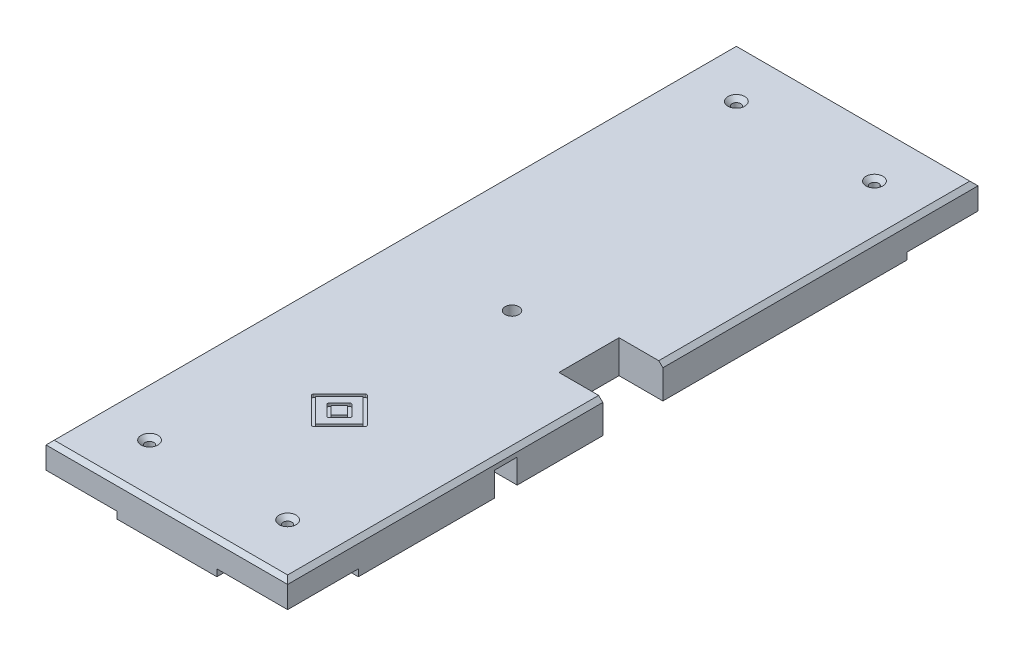
SolidWorks part; units mm, degrees
ref_plane "Front Plane" through (0, 0, 0) normal (0, 0, 1) x (1, 0, 0)
ref_plane "Top Plane" through (0, 0, 0) normal (0, 1, 0) x (1, 0, 0)
ref_plane "Right Plane" through (0, 0, 0) normal (1, 0, 0) x (0, 0, -1)
sketch "Sketch1" plane through (0, -20.7207, 0) normal (0, 1, 0) x (1, 0, 0)
  line L3 (6.005, -235.0339) -> (6.005, -194.0339)
  line L4 (6.005, -194.0339) -> (47.005, -194.0339)
  line L12 (47.005, 123.9661) -> (6.005, 123.9661)
  line L13 (47.005, -194.0339) -> (47.005, 123.9661)
  line L14 (6.005, -194.0339) -> (47.005, -194.0339)
  line L15 (6.005, -235.0339) -> (6.005, -194.0339)
  line L16 (-51.995, -235.0339) -> (6.005, -235.0339)
  line L17 (-51.995, -194.0339) -> (-51.995, -235.0339)
  line L18 (-92.995, -194.0339) -> (-51.995, -194.0339)
  line L19 (-92.995, 123.9661) -> (-92.995, -194.0339)
  line L20 (-51.995, 123.9661) -> (-92.995, 123.9661)
  line L21 (-51.995, 164.9661) -> (-51.995, 123.9661)
  line L22 (6.005, 164.9661) -> (-51.995, 164.9661)
  line L23 (6.005, 123.9661) -> (6.005, 164.9661)
  line L24 (47.005, 123.9661) -> (6.005, 123.9661)
  line L25 (47.005, -194.0339) -> (47.005, 123.9661)
  line L28 (-51.995, -235.0339) -> (6.005, -235.0339)
  line L29 (-51.995, -194.0339) -> (-51.995, -235.0339)
  line L30 (-92.995, -194.0339) -> (-51.995, -194.0339)
  line L31 (-92.995, 123.9661) -> (-92.995, -194.0339)
  line L32 (-51.995, 123.9661) -> (-92.995, 123.9661)
  line L33 (-51.995, 164.9661) -> (-51.995, 123.9661)
  line L34 (6.005, 164.9661) -> (-51.995, 164.9661)
  line L35 (6.005, 123.9661) -> (6.005, 164.9661)
  circle A1 centre (17.005, -225.0339) radius 2.5
  circle A2 centre (17.005, -225.0339) radius 2.5
  circle A3 centre (37.005, -205.0339) radius 2.5
  circle A4 centre (37.005, -205.0339) radius 2.5
  circle A5 centre (17.005, -205.0339) radius 2.5
  circle A6 centre (17.005, -205.0339) radius 2.5
  circle A7 centre (-62.995, -205.0339) radius 2.5
  circle A8 centre (-62.995, -205.0339) radius 2.5
  circle A9 centre (-62.995, -225.0339) radius 2.5
  circle A10 centre (-62.995, -225.0339) radius 2.5
  circle A11 centre (-82.995, -225.0339) radius 2.5
  circle A12 centre (-82.995, -225.0339) radius 2.5
  circle A13 centre (-82.995, -205.0339) radius 2.5
  circle A14 centre (-82.995, -205.0339) radius 2.5
  circle A15 centre (-62.995, 134.9661) radius 2.5
  circle A16 centre (-62.995, 134.9661) radius 2.5
  circle A17 centre (-62.995, 154.9661) radius 2.5
  circle A18 centre (-62.995, 154.9661) radius 2.5
  circle A19 centre (-82.995, 154.9661) radius 2.5
  circle A20 centre (-82.995, 154.9661) radius 2.5
  circle A21 centre (37.005, 134.9661) radius 2.5
  circle A22 centre (37.005, 134.9661) radius 2.5
  circle A23 centre (17.005, 134.9661) radius 2.5
  circle A24 centre (17.005, 134.9661) radius 2.5
  circle A25 centre (17.005, 154.9661) radius 2.5
  circle A26 centre (17.005, 154.9661) radius 2.5
  circle A27 centre (37.005, 154.9661) radius 2.5
  circle A28 centre (37.005, 154.9661) radius 2.5
  circle A29 centre (-82.995, 134.9661) radius 2.5
  circle A30 centre (-82.995, 134.9661) radius 2.5
  dimension "D1" = 0
  dimension "D2" = 0
  dimension "D3" = 0
  dimension "D4" = 0
  dimension "D5" = 0
  dimension "D6" = 0
  dimension "D7" = 0
  dimension "D8" = 0
  dimension "D9" = 0
  dimension "D10" = 0
  dimension "D11" = 0
  dimension "D12" = 0
  dimension "D13" = 0
  dimension "D14" = 0
  dimension "D15" = 0
  dimension "D16" = 0
extrude "Boss-Extrude1" add sketch "Sketch1" against normal up to surface (4 mm away) contours L31 L30 L29 L28 L3 L4 L25 L24 L35 L34 L33 L32
sketch "Sketch2" plane through (0, -20.7207, 0) normal (0, 1, 0) x (1, 0, 0)
  line L0 (-92.995, 164.9661) -> (47.005, 164.9661)
  line L1 (-92.995, 164.9661) -> (-92.995, -235.0339)
  line L2 (47.005, 164.9661) -> (47.005, -235.0339)
  line L3 (-92.995, -235.0339) -> (47.005, -235.0339)
  line L4 (-52.995, -235.0339) -> (-92.995, -235.0339) construction
extrude "Boss-Extrude2" add sketch "Sketch2" along normal blind 15.05
sketch "Sketch3" plane through (0, -20.7207, 0) normal (0, -1, 0) x (1, 0, 0)
  line L0 (-56.995, 225.0339) -> (-86.995, 225.0339) construction
  line L1 (-86.995, 229.0339) -> (-78.995, 229.0339)
  line L2 (-86.995, 229.0339) -> (-86.995, 199.0339)
  line L3 (-86.995, 199.0339) -> (-78.995, 199.0339)
  line L4 (-78.995, 229.0339) -> (-78.995, 199.0339)
  line L5 (-56.995, 221.0339) -> (-86.995, 221.0339)
  line L6 (-56.995, 221.0339) -> (-56.995, 229.0339)
  line L7 (-56.995, 229.0339) -> (-86.995, 229.0339)
  line L8 (-86.995, 221.0339) -> (-86.995, 229.0339)
  line L9 (-82.995, 229.0339) -> (-82.995, 199.0339) construction
  line L10 (-22.995, 235.0339) -> (-22.995, 201.9743) construction
  line L11 (6.005, 235.0339) -> (-51.995, 235.0339) construction
  line L12 (-92.995, 35.0339) -> (-2.995, 35.0339) construction
  line L13 (-92.995, 194.0339) -> (-92.995, -123.9661) construction
  line L14 (41.005, 199.0339) -> (33.005, 199.0339)
  line L15 (41.005, 229.0339) -> (41.005, 199.0339)
  line L16 (33.005, 229.0339) -> (33.005, 199.0339)
  line L17 (11.005, 221.0339) -> (11.005, 229.0339)
  line L18 (11.005, 221.0339) -> (41.005, 221.0339)
  line L19 (11.005, 229.0339) -> (41.005, 229.0339)
  line L20 (-22.995, -164.9661) -> (-22.995, -131.9065) construction
  line L21 (-82.995, -158.9661) -> (-82.995, -128.9661) construction
  line L22 (-56.995, -154.9661) -> (-86.995, -154.9661) construction
  line L23 (11.005, -158.9661) -> (41.005, -158.9661)
  line L24 (11.005, -150.9661) -> (41.005, -150.9661)
  line L25 (11.005, -150.9661) -> (11.005, -158.9661)
  line L26 (33.005, -158.9661) -> (33.005, -128.9661)
  line L27 (41.005, -158.9661) -> (41.005, -128.9661)
  line L28 (41.005, -128.9661) -> (33.005, -128.9661)
  line L29 (-86.995, -150.9661) -> (-86.995, -158.9661)
  line L30 (-56.995, -158.9661) -> (-86.995, -158.9661)
  line L31 (-56.995, -150.9661) -> (-56.995, -158.9661)
  line L32 (-56.995, -150.9661) -> (-86.995, -150.9661)
  line L33 (-78.995, -158.9661) -> (-78.995, -128.9661)
  line L34 (-86.995, -128.9661) -> (-78.995, -128.9661)
  line L35 (-86.995, -158.9661) -> (-86.995, -128.9661)
  line L36 (-86.995, -158.9661) -> (-78.995, -158.9661)
  circle A0 centre (-82.995, 225.0339) radius 2.5 construction
  circle A1 centre (-82.995, 225.0339) radius 2.5
  circle A2 centre (-82.995, -154.9661) radius 2.5
  dimension "D1" = 8
  dimension "D2" = 8
  dimension "D3" = 30
  dimension "D4" = 30
extrude "Cut-Extrude1" cut sketch "Sketch3" against normal blind 5 contours L18 L16 L14 L15 | L19 L16 L18 L15 | L19 L17 L18 L16 | L6 L7 L4 L5 | L4 L5 L2 L3 | L5 L4 L1 L2 A1 | A1 | L33 L30 L31 L32 | L35 L32 L33 L34 | L30 L33 L32 L29 A2 | A2 | L23 L27 L24 L26 | L23 L26 L24 L25 | L27 L28 L26 L24 region at (-82.995, -20.7207, 228.9207) region at (-67.995, -20.7207, 225.0339) region at (-82.995, -20.7207, 210.0339) region at (37.005, -20.7207, 210.0339) region at (37.005, -20.7207, 225.0339) region at (22.005, -20.7207, 225.0339) region at (22.005, -20.7207, -154.9661) region at (37.005, -20.7207, -154.9661) region at (37.005, -20.7207, -139.9661) region at (-82.995, -20.7207, -151.0793) region at (-82.995, -20.7207, -139.9661) region at (-67.995, -20.7207, -154.9661) region at (-82.995, -20.7207, 225.0339) region at (-82.995, -20.7207, -154.9661)
sketch "Sketch4" plane through (0, -20.7207, 0) normal (0, -1, 0) x (1, 0, 0)
  line L0 (-92.995, 235.0339) -> (47.005, -164.9661) construction
  line L2 (47.005, 235.0339) -> (-92.995, -164.9661) construction
  line L3 (-22.995, 35.0339) -> (-22.995, 293.1624) construction
  circle A0 centre (-62.995, -134.9661) radius 2.5 construction
  circle A1 centre (-62.995, -134.9661) radius 2.5
  circle A5 centre (17.005, -134.9661) radius 2.5
  circle A9 centre (-62.995, 205.0339) radius 2.5
  circle A10 centre (17.005, 205.0339) radius 2.5
extrude "Cut-Extrude2" cut sketch "Sketch4" against normal up to next
chamfer "Chamfer1" distance 2.38 8 edges at (-62.995, -5.6707, -132.4661) (17.005, -5.6707, -132.4661) (-22.995, -5.6707, -164.9661) (47.005, -5.6707, 35.0339) (-22.995, -5.6707, 235.0339) (-92.995, -5.6707, 35.0339) (-62.995, -5.6707, 207.5339) (17.005, -5.6707, 207.5339)
sketch "Sketch5" plane through (0, -5.6707, 0) normal (0, 1, 0) x (1, 0, 0)
  line L0 (47.005, -35.0339) -> (-92.995, -35.0339) construction
  line L1 (47.005, -235.0339) -> (47.005, 164.9661) construction
  line L2 (-92.995, 164.9661) -> (-92.995, -235.0339) construction
  line L3 (47.005, 164.9661) -> (-92.995, -235.0339) construction
  line L4 (47.005, -235.0339) -> (-92.995, 164.9661) construction
  circle A0 centre (-22.995, -35.0339) radius 4
  point P15 (-22.995, -35.0339)
  dimension "D1" = 8
extrude "Cut-Extrude3" cut sketch "Sketch5" against normal up to next contours A0
sketch "Sketch6" plane through (0, -5.6707, 0) normal (0, 1, 0) x (1, 0, 0)
  line L0 (-22.995, -35.0339) -> (-22.995, -135.0339) construction
  line L1 (-22.995, -120.0339) -> (-22.995, -135.0339) construction
  line L2 (-22.995, -135.0339) -> (-7.995, -135.0339) construction
  line L3 (-29.0147, -135.0339) -> (-22.995, -129.0141) construction
  line L4 (-28.396, -135.6526) -> (-22.3762, -129.6328)
  line L5 (-92.995, 164.9661) -> (47.005, -235.0339) construction
  line L6 (47.005, 164.9661) -> (-92.995, -235.0339) construction
  line L9 (-29.6334, -134.4151) -> (-23.6137, -128.3954)
  line L10 (-22.995, -120.0339) -> (-37.995, -135.0339) construction
  line L13 (-22.3762, -120.6526) -> (-37.3762, -135.6526)
  line L14 (-23.6137, -119.4151) -> (-38.6137, -134.4151)
  line L19 (-16.9752, -135.0339) -> (-22.995, -141.0536) construction
  line L20 (-17.5939, -134.4151) -> (-23.6137, -140.4349)
  line L21 (-16.3565, -135.6526) -> (-22.3762, -141.6723)
  line L24 (-23.6137, -120.6526) -> (-8.6137, -135.6526)
  line L25 (-22.3762, -119.4151) -> (-7.3762, -134.4151)
  line L26 (-29.0147, -135.0339) -> (-22.995, -141.0536) construction
  line L27 (-22.995, -120.0339) -> (-7.995, -135.0339) construction
  line L28 (-28.396, -134.4151) -> (-22.3762, -140.4349)
  line L33 (-29.6334, -135.6526) -> (-23.6137, -141.6723)
  line L34 (-22.995, -150.0339) -> (-37.995, -135.0339) construction
  line L39 (-22.3762, -149.4151) -> (-37.3762, -134.4151)
  line L42 (-23.6137, -150.6526) -> (-38.6137, -135.6526)
  line L43 (-22.995, -150.0339) -> (-7.995, -135.0339) construction
  line L46 (-16.3565, -134.4151) -> (-22.3762, -128.3954)
  line L47 (-17.5939, -135.6526) -> (-23.6137, -129.6328)
  line L50 (-16.9752, -135.0339) -> (-22.995, -129.0141) construction
  line L51 (-23.6137, -149.4151) -> (-8.6137, -134.4151)
  line L52 (-22.3762, -150.6526) -> (-7.3762, -135.6526)
  arc A11 (-7.3762, -134.4151) -> (-8.6137, -135.6526) centre (-7.995, -135.0339) cw
  arc A12 (-23.6137, -120.6526) -> (-22.3762, -119.4151) centre (-22.995, -120.0339) cw
  arc A21 (-17.5939, -135.6526) -> (-16.3565, -134.4151) centre (-16.9752, -135.0339) ccw
  arc A22 (-22.3762, -128.3954) -> (-23.6137, -129.6328) centre (-22.995, -129.0141) ccw
  arc A23 (-28.396, -135.6526) -> (-29.6334, -134.4151) centre (-29.0147, -135.0339) cw
  arc A24 (-23.6137, -128.3954) -> (-22.3762, -129.6328) centre (-22.995, -129.0141) cw
  arc A25 (-22.3762, -120.6526) -> (-23.6137, -119.4151) centre (-22.995, -120.0339) ccw
  arc A26 (-38.6137, -134.4151) -> (-37.3762, -135.6526) centre (-37.995, -135.0339) ccw
  arc A27 (-17.5939, -134.4151) -> (-16.3565, -135.6526) centre (-16.9752, -135.0339) cw
  arc A28 (-22.3762, -141.6723) -> (-23.6137, -140.4349) centre (-22.995, -141.0536) cw
  arc A29 (-28.396, -134.4151) -> (-29.6334, -135.6526) centre (-29.0147, -135.0339) ccw
  arc A30 (-23.6137, -141.6723) -> (-22.3762, -140.4349) centre (-22.995, -141.0536) ccw
  arc A31 (-22.3762, -149.4151) -> (-23.6137, -150.6526) centre (-22.995, -150.0339) cw
  arc A32 (-38.6137, -135.6526) -> (-37.3762, -134.4151) centre (-37.995, -135.0339) cw
  arc A33 (-23.6137, -149.4151) -> (-22.3762, -150.6526) centre (-22.995, -150.0339) ccw
  arc A34 (-7.3762, -135.6526) -> (-8.6137, -134.4151) centre (-7.995, -135.0339) ccw
  point P17 (-26.0048, -132.024)
  point P23 (-30.495, -127.5339)
  point P30 (-19.9851, -138.0437)
  point P37 (-26.0048, -138.0437)
  point P46 (-30.495, -142.5339)
  point P48 (-15.495, -127.5339)
  point P57 (-15.495, -142.5339)
  point P82 (-19.9851, -132.024)
  dimension "D4" = 4.6
  dimension "D6" = 8.5132
  dimension "D1" = 21.2132
  dimension "D2" = 8.9803
  dimension "D3" = 1.75
  dimension "D7" = 15
  dimension "D5" = 1.75
  dimension "D8" = 100
extrude "Cut-Extrude4" cut sketch "Sketch6" against normal blind 1.75 contours L24 A11 L25 A12 | L52 A34 L51 A33 | L42 A32 L39 A31 | L14 A26 L13 A25 | L9 A24 L4 A23 | L46 A22 L47 A21 | L21 A28 L20 A27 | L33 A30 L28 A29
sketch "Sketch7" plane through (0, -24.7207, 0) normal (0, -1, 0) x (1, 0, 0)
  line L1 (-0.995, 168.0339) -> (-44.995, 168.0339)
  line L2 (-0.995, 168.0339) -> (-0.995, 102.0339)
  line L3 (-0.995, 102.0339) -> (-44.995, 102.0339)
  line L5 (-44.995, 168.0339) -> (-44.995, 102.0339)
  line L6 (-0.995, 168.0339) -> (-44.995, 102.0339) construction
  line L7 (-0.995, 102.0339) -> (-44.995, 168.0339) construction
  line L10 (-0.995, 115.0339) -> (49.005, 115.0339)
  line L11 (-0.995, 115.0339) -> (-0.995, 102.0339)
  line L12 (-92.995, -123.9661) -> (-51.995, -123.9661)
  line L13 (-51.995, -123.9661) -> (-51.995, -164.9661)
  line L14 (-51.995, -164.9661) -> (6.005, -164.9661)
  line L15 (6.005, -164.9661) -> (6.005, -123.9661)
  line L16 (6.005, -123.9661) -> (47.005, -123.9661)
  line L17 (47.005, -123.9661) -> (47.005, 194.0339)
  line L18 (47.005, 194.0339) -> (6.005, 194.0339)
  line L19 (47.005, 194.0339) -> (6.005, 194.0339)
  line L20 (6.005, 235.0339) -> (-51.995, 235.0339)
  line L21 (-51.995, 235.0339) -> (-51.995, 194.0339)
  line L22 (-51.995, 194.0339) -> (-92.995, 194.0339)
  line L23 (-92.995, 194.0339) -> (-92.995, -123.9661)
  line L24 (-92.995, -123.9661) -> (-51.995, -123.9661)
  line L25 (-51.995, -123.9661) -> (-51.995, -164.9661)
  line L26 (-51.995, -164.9661) -> (6.005, -164.9661)
  line L27 (6.005, -164.9661) -> (6.005, -123.9661)
  line L28 (6.005, -123.9661) -> (47.005, -123.9661)
  line L29 (47.005, -123.9661) -> (47.005, 194.0339)
  line L32 (6.005, 235.0339) -> (-51.995, 235.0339)
  line L33 (-51.995, 235.0339) -> (-51.995, 194.0339)
  line L34 (-51.995, 194.0339) -> (-92.995, 194.0339)
  line L35 (-92.995, 194.0339) -> (-92.995, -123.9661)
  line L38 (-0.995, 102.0339) -> (49.005, 102.0339)
  line L39 (49.005, 115.0339) -> (49.005, 102.0339)
  line L55 (6.005, 194.0339) -> (6.005, 235.0339)
  line L56 (6.005, 194.0339) -> (6.005, 235.0339)
  point P2 (-22.995, 135.0339)
  point P8 (-22.995, 135.0339)
  point P78 (-3.6137, 160.0339)
  dimension "D2" = 44
  dimension "D3" = 66
  dimension "D4" = 50
  dimension "D5" = 13
  dimension "D1" = 0
extrude "Cut-Extrude5" cut sketch "Sketch7" along direction (0, -1, 0) on the side against the normal offset from surface (14.05 mm away) 5 contours L5 L3 L2 L1 | L11 L10 L39 L38 up to face at (-22.995, -5.6707, 135.0339)
sketch "Sketch8" plane through (0, -5.6707, 0) normal (0, 1, 0) x (1, 0, 0)
  line L0 (47.005, -35.0339) -> (-93.7041, -35.0339) construction
  line L1 (47.005, -235.0339) -> (47.005, 164.9661) construction
  line L3 (21.6131, -52.445) -> (47.005, -52.445)
  line L4 (21.6131, -52.445) -> (21.6131, -17.6228)
  line L5 (21.6131, -17.6228) -> (47.005, -17.6228)
  line L6 (47.005, -52.445) -> (47.005, -17.6228)
  line L7 (21.6131, -52.445) -> (47.005, -17.6228) construction
  line L8 (21.6131, -17.6228) -> (47.005, -52.445) construction
  point P4 (34.3091, -35.0339)
extrude "Cut-Extrude6" cut sketch "Sketch8" against normal up to next
